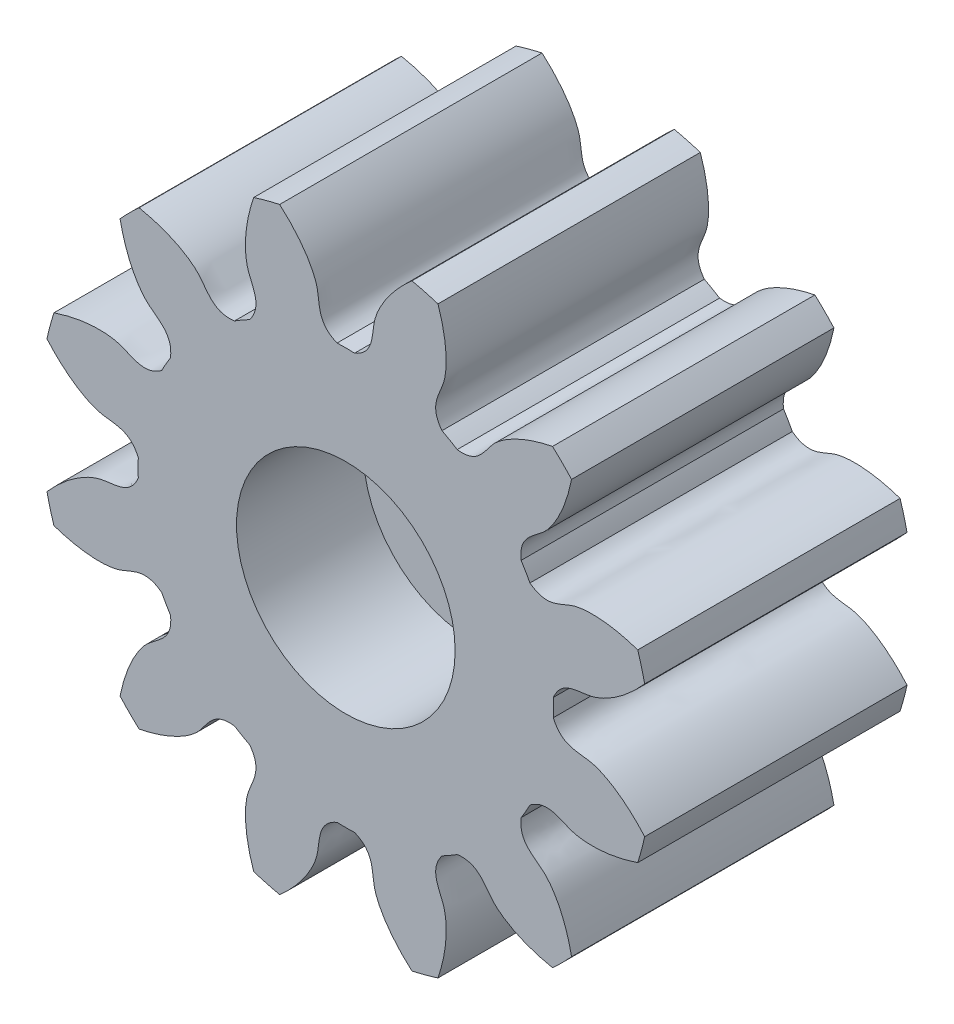
SolidWorks part; units mm, degrees
ref_plane "前视基准面" through (0, 0, 0) normal (0, 0, 1) x (1, 0, 0)
ref_plane "上视基准面" through (0, 0, 0) normal (0, 1, 0) x (1, 0, 0)
ref_plane "右视基准面" through (0, 0, 0) normal (1, 0, 0) x (0, 0, -1)
sketch "草图1" plane through (0, 0, 0) normal (0, 0, 1) x (1, 0, 0)
  circle A0 centre (0, 0) radius 7
extrude "凸台-拉伸1" add sketch "草图1" along normal blind 6
ref_axis "基准轴1" through (0, 0, -0.3) along (0, 0, 1)
sketch "草图2" plane through (0, 0, 0) normal (0, 0, 1) x (1, 0, 0)
  line L0 (0, 0) -> (0, 7) construction
  circle A0 centre (0, 0) radius 7 construction
  arc A1 (0.2008, 4.7458) -> (-0.2008, 4.7458) centre (0, 0) ccw
  arc A2 (3.4976, 7.895) -> (-3.4976, 7.895) centre (0, 0) ccw
  spline S0 degree 3 poles (0.2008, 4.7458) (0.6808, 4.9493) (0.5744, 5.3448) (0.6762, 5.6895) (0.6826, 5.7099) (0.6902, 5.7323) (0.699, 5.7567) (0.7092, 5.783) (0.7206, 5.8112) (0.7336, 5.8413) (0.748, 5.8731) (0.7641, 5.9067) (0.7819, 5.9419) (0.8014, 5.9788) (0.8227, 6.0172) (0.846, 6.0572) (0.8712, 6.0986) (0.8984, 6.1415) (0.9277, 6.1856) (0.9592, 6.231) (0.993, 6.2776) (1.029, 6.3253) (1.0673, 6.374) (1.1081, 6.4238) (1.1513, 6.4744) (1.197, 6.5258) (1.2452, 6.5779) (1.296, 6.6307) (1.3495, 6.6841) (1.4057, 6.7379) (1.4646, 6.7922) (1.5262, 6.8467) (1.5907, 6.9015) (1.658, 6.9564) (1.7281, 7.0113) (1.8012, 7.0662) (1.8771, 7.1209) (1.956, 7.1753) (2.0378, 7.2295) (2.1226, 7.2831) (2.2104, 7.3363) (2.3012, 7.3888) (2.395, 7.4406) (2.4918, 7.4915) (2.5916, 7.5415) (2.6944, 7.5904) (2.8003, 7.6383) (2.9092, 7.6848) (3.021, 7.7301) (3.1359, 7.7739) (3.2944, 7.8307) (3.4156, 7.8701) (3.4976, 7.895) knots 0 0 0 0 0.218015 0.222044 0.226546 0.231522 0.236972 0.242897 0.249295 0.256167 0.263513 0.271332 0.279626 0.288394 0.297636 0.307351 0.317541 0.328204 0.339341 0.350953 0.363038 0.375597 0.38863 0.402137 0.416118 0.430573 0.445502 0.460904 0.476781 0.493132 0.509956 0.527255 0.545027 0.563273 0.581994 0.601188 0.620856 0.640998 0.661614 0.682704 0.704268 0.726305 0.748817 0.771803 0.795262 0.819196 0.843603 0.868484 0.89384 0.919669 0.945972 1 1 1 1
  spline S1 degree 3 poles (-0.2008, 4.7458) (-0.6808, 4.9493) (-0.5744, 5.3448) (-0.6762, 5.6895) (-0.6826, 5.7099) (-0.6902, 5.7323) (-0.699, 5.7567) (-0.7092, 5.783) (-0.7206, 5.8112) (-0.7336, 5.8413) (-0.748, 5.8731) (-0.7641, 5.9067) (-0.7819, 5.9419) (-0.8014, 5.9788) (-0.8227, 6.0172) (-0.846, 6.0572) (-0.8712, 6.0986) (-0.8984, 6.1415) (-0.9277, 6.1856) (-0.9592, 6.231) (-0.993, 6.2776) (-1.029, 6.3253) (-1.0673, 6.374) (-1.1081, 6.4238) (-1.1513, 6.4744) (-1.197, 6.5258) (-1.2452, 6.5779) (-1.296, 6.6307) (-1.3495, 6.6841) (-1.4057, 6.7379) (-1.4646, 6.7922) (-1.5262, 6.8467) (-1.5907, 6.9015) (-1.658, 6.9564) (-1.7281, 7.0113) (-1.8012, 7.0662) (-1.8771, 7.1209) (-1.956, 7.1753) (-2.0378, 7.2295) (-2.1226, 7.2831) (-2.2104, 7.3363) (-2.3012, 7.3888) (-2.395, 7.4406) (-2.4918, 7.4915) (-2.5916, 7.5415) (-2.6944, 7.5904) (-2.8003, 7.6383) (-2.9092, 7.6848) (-3.021, 7.7301) (-3.1359, 7.7739) (-3.2944, 7.8307) (-3.4156, 7.8701) (-3.4976, 7.895) knots 0 0 0 0 0.218015 0.222044 0.226546 0.231522 0.236972 0.242897 0.249295 0.256167 0.263513 0.271332 0.279626 0.288394 0.297636 0.307351 0.317541 0.328204 0.339341 0.350953 0.363038 0.375597 0.38863 0.402137 0.416118 0.430573 0.445502 0.460904 0.476781 0.493132 0.509956 0.527255 0.545027 0.563273 0.581994 0.601188 0.620856 0.640998 0.661614 0.682704 0.704268 0.726305 0.748817 0.771803 0.795262 0.819196 0.843603 0.868484 0.89384 0.919669 0.945972 1 1 1 1
extrude "切除-拉伸1" cut sketch "草图2" along normal through all
pattern_circular "阵列(圆周)1" count 12 every 30 about axis through (0, 0, -0.3) along (0, 0, 1) of "切除-拉伸1"
sketch "草图3" plane through (0, 0, 0) normal (0, 0, 1) x (1, 0, 0)
  circle A0 centre (0, 0) radius 6 construction
  dimension "Dn" = 12
sketch "草图4" plane through (0, 0, 6) normal (0, 0, 1) x (1, 0, 0)
  circle A0 centre (0, 0) radius 2.5
  dimension "D1" = 5
extrude "切除-拉伸3" cut sketch "草图4" against normal blind 2.9
sketch "草图5" plane through (0, 0, 3.1) normal (0, 0, 1) x (1, 0, 0)
  circle A0 centre (0, 0) radius 0.9
  dimension "D1" = 1.8
extrude "切除-拉伸5" cut sketch "草图5" against normal blind 3.5
